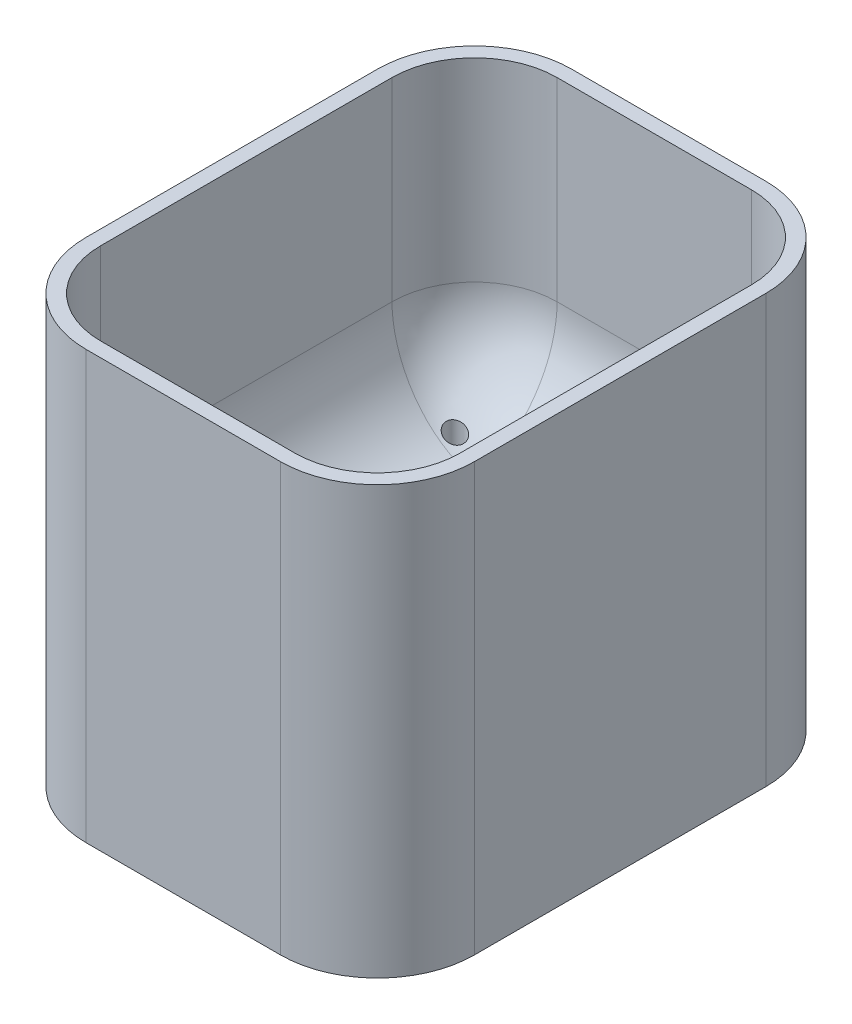
SolidWorks part; units mm, degrees
ref_plane "Plano frontal" through (0, 0, 0) normal (0, 0, 1) x (1, 0, 0)
ref_plane "Plano superior" through (0, 0, 0) normal (0, 1, 0) x (1, 0, 0)
ref_plane "Plano direito" through (0, 0, 0) normal (1, 0, 0) x (0, 0, -1)
sketch "Esboço1" plane through (0, 0, 0) normal (0, 1, 0) x (1, 0, 0)
  line L1 (-10, -25) -> (10, -25)
  line L2 (-20, -15) -> (-20, 15)
  line L3 (-10, 25) -> (10, 25)
  line L4 (20, -15) -> (20, 15)
  line L5 (-20, -25) -> (20, 25) construction
  line L6 (-20, 25) -> (20, -25) construction
  arc A0 (10, 25) -> (20, 15) centre (10, 15) cw
  arc A1 (10, -25) -> (20, -15) centre (10, -15) ccw
  arc A2 (-10, -25) -> (-20, -15) centre (-10, -15) cw
  arc A3 (-20, 15) -> (-10, 25) centre (-10, 15) cw
  point P0 (0, 0)
  dimension "D3" = 10
  dimension "D1" = 40
  dimension "D2" = 50
extrude "Ressalto-extrusão1" add sketch "Esboço1" along normal blind 2 and the other way blind 12
sketch "Esboço2" plane through (0, 2, 0) normal (0, 1, 0) x (1, 0, 0)
  line L6 (-20, 15) -> (-20, -15)
  line L7 (-10, -25) -> (10, -25)
  line L8 (20, -15) -> (20, 15)
  line L9 (10, 25) -> (-10, 25)
  line L10 (-18.5, 15) -> (-18.5, -15)
  line L11 (-10, -23.5) -> (10, -23.5)
  line L12 (18.5, -15) -> (18.5, 15)
  line L13 (10, 23.5) -> (-10, 23.5)
  line L14 (-18.5, 15) -> (-18.5, -15)
  line L15 (-10, -23.5) -> (10, -23.5)
  line L16 (18.5, -15) -> (18.5, 15)
  line L17 (10, 23.5) -> (-10, 23.5)
  arc A6 (-20, -15) -> (-10, -25) centre (-10, -15) ccw
  arc A7 (10, -25) -> (20, -15) centre (10, -15) ccw
  arc A8 (20, 15) -> (10, 25) centre (10, 15) ccw
  arc A9 (-10, 25) -> (-20, 15) centre (-10, 15) ccw
  arc A10 (-18.5, -15) -> (-10, -23.5) centre (-10, -15) ccw
  arc A11 (10, -23.5) -> (18.5, -15) centre (10, -15) ccw
  arc A12 (18.5, 15) -> (10, 23.5) centre (10, 15) ccw
  arc A13 (-10, 23.5) -> (-18.5, 15) centre (-10, 15) ccw
  arc A14 (-18.5, -15) -> (-10, -23.5) centre (-10, -15) ccw
  arc A15 (10, -23.5) -> (18.5, -15) centre (10, -15) ccw
  arc A16 (18.5, 15) -> (10, 23.5) centre (10, 15) ccw
  arc A17 (-10, 23.5) -> (-18.5, 15) centre (-10, 15) ccw
  dimension "D1" = 1.5
  dimension "D2" = 1.5
extrude "Ressalto-extrusão2" add sketch "Esboço2" along normal blind 30
fillet "Filete1" radius 10 8 edges at (0, 2, -23.5) (16.0104, 2, -21.0104) (18.5, 2, 0) (16.0104, 2, 21.0104) (0, 2, 23.5) (-16.0104, 2, 21.0104) (-18.5, 2, 0) (-16.0104, 2, -21.0104)
sketch "Esboço3" plane through (0, -12, 0) normal (0, -1, 0) x (1, 0, 0)
  line L0 (15.6558, -13.8645) -> (15.6558, 10.1355)
  line L1 (-4.5442, -13.8645) -> (15.6558, -13.8645)
  line L2 (-4.5442, -18.6145) -> (-20, -18.6145)
  line L3 (-4.5442, -18.6145) -> (-4.5442, -13.8645)
  line L4 (-4.5442, 14.8855) -> (-20, 15)
  line L5 (-20, -18.6145) -> (-20, 15)
  line L6 (-4.5442, 10.1355) -> (-4.5442, 14.8855)
  line L7 (11.1558, 10.1355) -> (11.1558, 14.8855)
  line L8 (11.1558, 14.8855) -> (6.1558, 14.8855)
  line L9 (6.1558, 10.1355) -> (6.1558, 14.8855)
  line L10 (15.6558, 10.1355) -> (11.1558, 10.1355)
  line L11 (6.1558, 10.1355) -> (-4.5442, 10.1355)
extrude "Corte-extrusão1" cut sketch "Esboço3" against normal blind 12
sketch "Esboço4" plane through (0, 0, 0) normal (0, -1, 0) x (1, 0, 0)
  circle A0 centre (-12.5617, -15.5402) radius 1
  dimension "D1" = 2
extrude "Corte-extrusão2" cut sketch "Esboço4" against normal blind 12
sketch "Esboço5" plane through (0, 0, 0) normal (0, -1, 0) x (1, 0, 0)
  circle A0 centre (-12.5617, -15.5402) radius 1
  circle A1 centre (-12.5617, -15.5402) radius 2
  dimension "D1" = 4
extrude "Ressalto-extrusão3" add sketch "Esboço5" along normal blind 7
